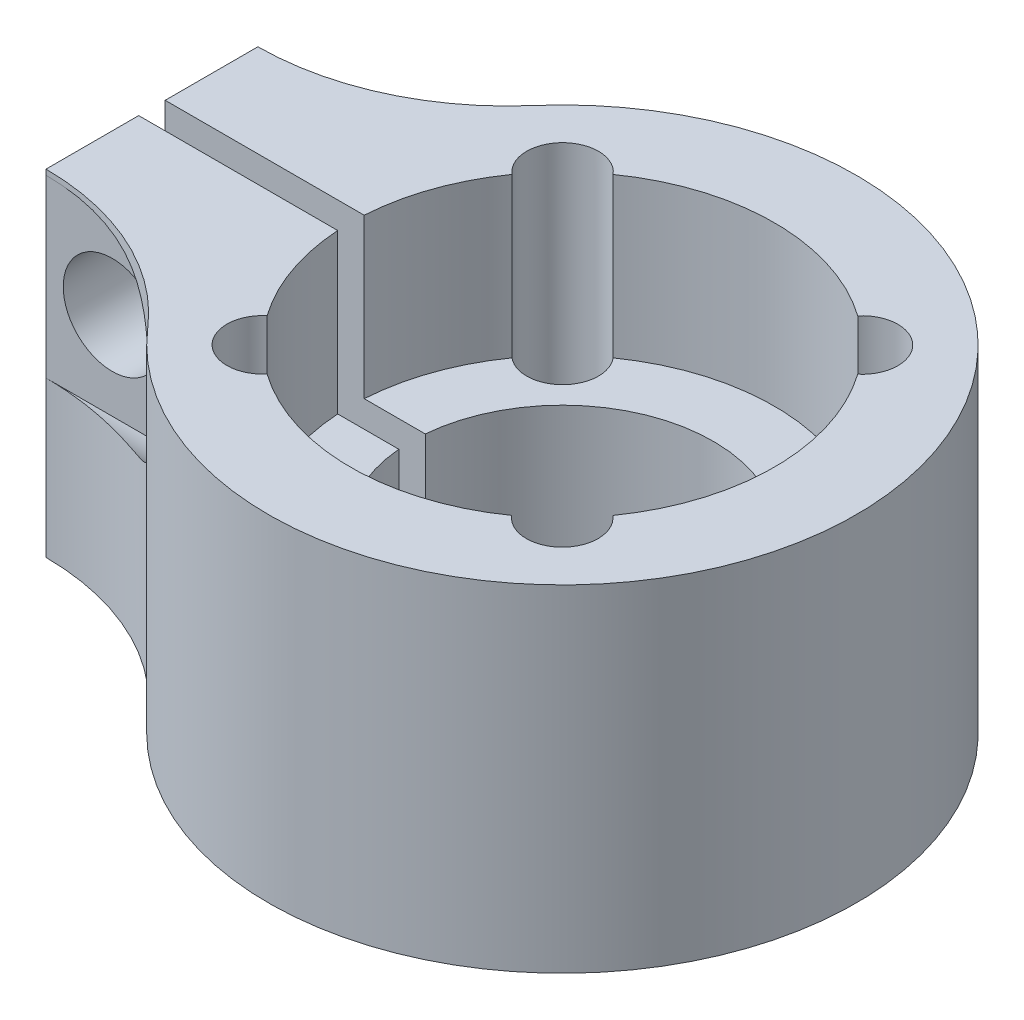
SolidWorks part; units mm, degrees
material "6061 Alloy"
ref_plane "Front Plane" through (0, 0, 0) normal (0, 0, 1) x (1, 0, 0)
ref_plane "Top Plane" through (0, 0, 0) normal (0, 1, 0) x (1, 0, 0)
ref_plane "Right Plane" through (0, 0, 0) normal (1, 0, 0) x (0, 0, -1)
sketch "Sketch1" plane through (0, 0, 0) normal (0, 0, 1) x (1, 0, 0)
  line L0 (0, 9.3884) -> (0, -5.3933) construction
  line L1 (5.7, 0) -> (8, 0)
  line L2 (8, 0) -> (8, 6)
  line L3 (8, 6) -> (11.1, 6)
  line L4 (11.1, 6) -> (11.1, -6.7)
  line L5 (11.1, -6.7) -> (5.7, -6.7)
  line L6 (5.7, -6.7) -> (5.7, 0)
  dimension "D1" = 5.7
  dimension "D2" = 8
  dimension "D3" = 6.7
  dimension "D4" = 11.1
  dimension "D5" = 12.7
revolve "Revolve1" add sketch "Sketch1" angle 360 about L0
sketch "Sketch2" plane through (0, 6, 0) normal (0, 1, 0) x (1, 0, 0)
  circle A0 centre (5.66, 5.6537) radius 1.355
  circle A1 centre (0, 0) radius 8 construction
  dimension "D1" = 5.66
  dimension "D2" = 2.71
extrude "Cut-Extrude1" cut sketch "Sketch2" against normal up to surface (12.7 mm away) up to face at (0, -6.7, 11.1)
pattern_circular "CirPattern1" count 4 over 360 about axis through (0, 9.3884, 0) along (0, -1, 0) of "Cut-Extrude1"
sketch "Sketch3" plane through (0, 6, 0) normal (0, 1, 0) x (1, 0, 0)
  line L0 (0, 0) -> (-17.2725, 0) construction
  line L1 (-15.5, 4) -> (-10.3542, 4)
  line L2 (-15.5, 4) -> (-15.5, -4)
  line L3 (-15.5, -4) -> (-10.3542, -4)
  line L4 (-10.3542, 4) -> (-10.3542, -4)
  circle A0 centre (0, 0) radius 11.1 construction
  dimension "D1" = 8
  dimension "D2" = 15.5
extrude "Extrude1" add sketch "Sketch3" against normal up to surface (12.7 mm away) up to face at (-5.6537, -6.7, -4.305)
fillet "Fillet1" radius 9.448 2 edges at (-10.3542, -0.35, -4) (-10.3542, -0.35, 4)
sketch "Sketch4" plane through (0, 6, 0) normal (0, 1, 0) x (1, 0, 0)
  line L0 (0, 0) -> (-15.5, 0) construction
  line L1 (-15.5, 4) -> (-15.5, -4) construction
  line L3 (-15.5, 0.5) -> (-5.5, 0.5)
  line L4 (-15.5, 0.5) -> (-15.5, -0.5)
  line L5 (-15.5, -0.5) -> (-5.5, -0.5)
  line L6 (-5.5, 0.5) -> (-5.5, -0.5)
  dimension "D1" = 1
  dimension "D2" = 10
extrude "Cut-Extrude2" cut sketch "Sketch4" against normal up to surface (12.7 mm away) up to face at (-5.6537, -6.7, -4.305)
sketch "Sketch5" plane through (-15.5, 0, 0) normal (-1, 0, 0) x (0, 0, 1)
  line L0 (4, 5.8) -> (4, -0.8329)
  line L1 (4, -6.7) -> (4, 6) construction
  line L2 (0.5, 6) -> (4, 6) construction
  arc A0 (4, 5.8) -> (4, -0.8329) centre (3.4607, 2.4836) cw
  dimension "D1" = 3.36
  dimension "D2" = 0.2
  dimension "D3" = 0.5393
extrude "Cut-Extrude3" cut sketch "Sketch5" against normal blind 6
sketch "Sketch6" plane through (0, 0, 4) normal (0, 0, 1) x (1, 0, 0)
  line L0 (-11.15, 2.4836) -> (-14.85, 2.4836) construction
  line L4 (-15.5, 5.8) -> (-15.5, -0.8329) construction
  circle A0 centre (-13, 2.4836) radius 1.85
  point P6 (-15.5, 2.4836)
  dimension "D1" = 3.7
  dimension "D2" = 2.5
extrude "Cut-Extrude4" cut sketch "Sketch6" against normal up to surface (3.5 mm away) up to face at (-9.7208, -0.2333, 0.5)
sketch "Sketch7" plane through (0, 0, -0.5) normal (0, 0, 1) x (1, 0, 0)
  circle A0 centre (-13, 2.4836) radius 1.3525
  circle A1 centre (-13, 2.4836) radius 1.85 construction
  dimension "D1" = 2.705
extrude "Cut-Extrude5" cut sketch "Sketch7" against normal up to surface (4.3373 mm away) up to face at (-11.7695, -0.35, -5.2473)
